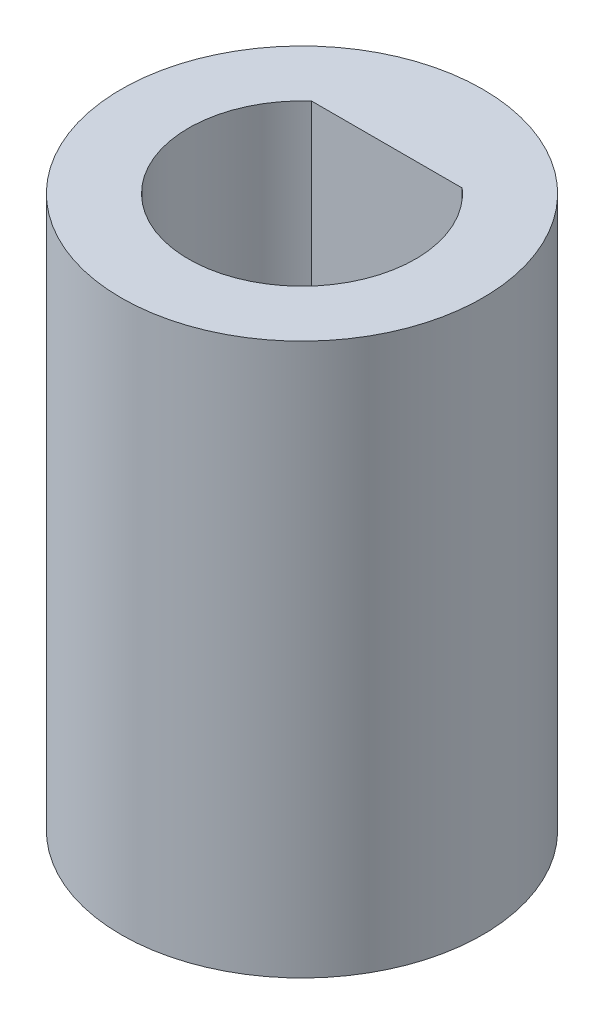
SolidWorks part; units mm, degrees
ref_plane "Front Plane" through (0, 0, 0) normal (0, 0, 1) x (1, 0, 0)
ref_plane "Top Plane" through (0, 0, 0) normal (0, 1, 0) x (1, 0, 0)
ref_plane "Right Plane" through (0, 0, 0) normal (1, 0, 0) x (0, 0, -1)
sketch "Sketch1" plane through (0, 0, 0) normal (0, 1, 0) x (1, 0, 0)
  line L0 (-2.2394, 2.525) -> (2.2394, 2.525) construction
  circle A0 centre (0, 0) radius 5.375
  circle A1 centre (0, 0) radius 3.375 construction
  arc A2 (-2.2394, 2.525) -> (2.2394, 2.525) centre (0, 0) ccw construction
  point P6 (0, -3.375)
  dimension "D1" = 6.75
  dimension "D2" = 2
  dimension "D3" = 5.9
extrude "Boss-Extrude1" add sketch "Sketch1" against normal blind 16.4
ref_plane "Plane1" through (0, 0, 0) normal (0, 1, 0) x (1, 0, 0)
ref_axis "Axis1" through (0, 1.27, 0) along (0, -1, 0)
sketch "Sketch2" plane through (0, 0, 0) normal (0, 0, 1) x (1, 0, 0)
  line L0 (5.6375, 0) -> (-5.6375, 0) construction
  circle A0 centre (0, -18.75) radius 18.75
  dimension "D1" = 37.5
sketch "Sketch3" plane through (0, 0, 0) normal (0, 1, 0) x (1, 0, 0)
  line L0 (-2.2394, 2.525) -> (2.2394, 2.525) construction
  line L1 (-2.2394, 2.525) -> (2.2394, 2.525)
  circle A0 centre (0, 0) radius 3.375 construction
  arc A1 (-2.2394, 2.525) -> (2.2394, 2.525) centre (0, 0) ccw
extrude "Cut-Extrude1" cut sketch "Sketch3" against normal through all
